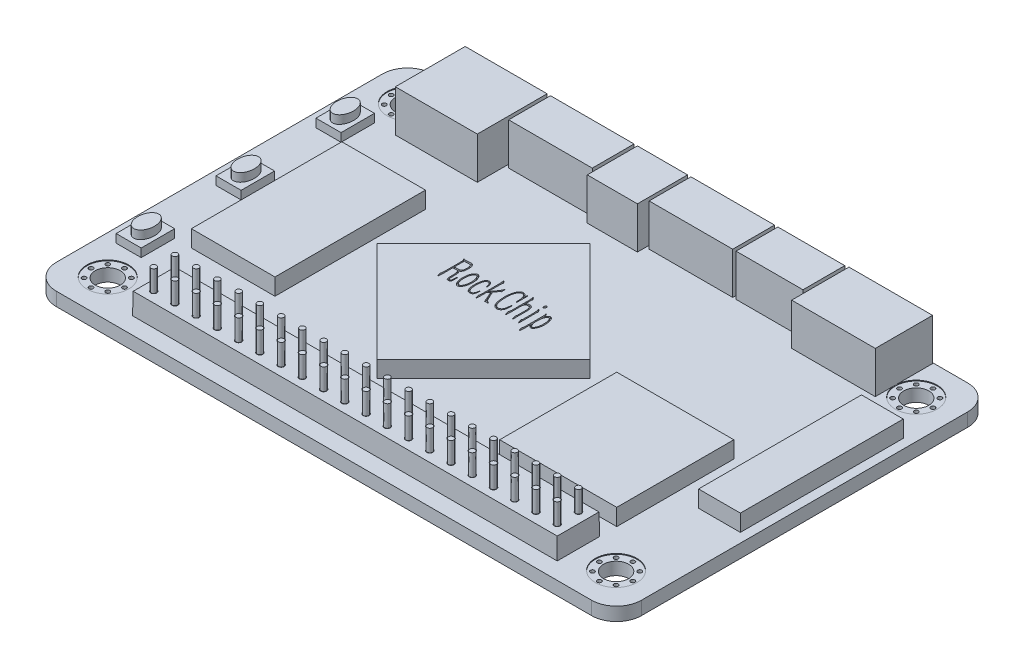
SolidWorks part; units mm, degrees
ref_plane "前视基准面" through (0, 0, 0) normal (0, 0, 1) x (1, 0, 0)
ref_plane "上视基准面" through (0, 0, 0) normal (0, 1, 0) x (1, 0, 0)
ref_plane "右视基准面" through (0, 0, 0) normal (1, 0, 0) x (0, 0, -1)
other "Configuration Table"
sketch "草图1" plane through (0, 0, 0) normal (0, 1, 0) x (1, 0, 0)
  line L0 (0, 33.0521) -> (0, -50.1271) construction
  line L1 (-32, 22.5) -> (32, 22.5)
  line L2 (-35, 19.5) -> (-35, -19.5)
  line L3 (-32, -22.5) -> (32, -22.5)
  line L4 (35, 19.5) -> (35, -19.5)
  line L5 (-35, 22.5) -> (35, -22.5) construction
  line L6 (-35, -22.5) -> (35, 22.5) construction
  line L7 (45.8676, 0) -> (-69.9838, 0) construction
  line L8 (-30.4, 17.95) -> (-30.4, -17.95) construction
  line L9 (-33.4, 13.95) -> (-30.4, 13.95)
  line L10 (-33.4, 13.95) -> (-33.4, 9.95)
  line L11 (-33.4, 9.95) -> (-30.4, 9.95)
  line L12 (-30.4, 13.95) -> (-30.4, 9.95)
  line L13 (-33.4, 13.95) -> (-30.4, 9.95) construction
  line L14 (-33.4, 9.95) -> (-30.4, 13.95) construction
  line L15 (-33.4, 2) -> (-30.4, 2)
  line L16 (-33.4, 2) -> (-33.4, -2)
  line L17 (-33.4, -2) -> (-30.4, -2)
  line L18 (-30.4, 2) -> (-30.4, -2)
  line L19 (-33.4, 2) -> (-30.4, -2) construction
  line L20 (-33.4, -2) -> (-30.4, 2) construction
  line L21 (-33.4, -9.95) -> (-30.4, -9.95)
  line L22 (-33.4, -9.95) -> (-33.4, -13.95)
  line L23 (-33.4, -13.95) -> (-30.4, -13.95)
  line L24 (-30.4, -9.95) -> (-30.4, -13.95)
  line L25 (-33.4, -9.95) -> (-30.4, -13.95) construction
  line L26 (-33.4, -13.95) -> (-30.4, -9.95) construction
  line L27 (-36.5276, -17.95) -> (-25.6215, -17.95) construction
  line L28 (-30.4, -23.6201) -> (-30.4, -14.4561) construction
  line L29 (-27.6395, -15.1895) -> (-32.9892, -20.5392) construction
  line L30 (-32.837, -15.513) -> (-27.2268, -21.1232) construction
  line L31 (-30.4, -24.4793) -> (-30.4, -15.3152) construction
  line L32 (-32.2706, -22.5293) -> (-32.2706, -13.3652) construction
  circle A0 centre (-30.4, -17.95) radius 1.5
  circle A1 centre (30.4, -17.95) radius 1.5
  circle A2 centre (-30.4, 17.95) radius 1.5
  circle A3 centre (-30.4, -17.95) radius 2.5
  circle A4 centre (30.4, 17.95) radius 1.5
  circle A5 centre (30.4, 17.95) radius 2.5
  circle A6 centre (30.4, -17.95) radius 2.5
  circle A7 centre (-30.4, 17.95) radius 2.5
  arc A8 (32, -22.5) -> (35, -19.5) centre (32, -19.5) ccw
  arc A9 (32, 22.5) -> (35, 19.5) centre (32, 19.5) cw
  arc A10 (-32, 22.5) -> (-35, 19.5) centre (-32, 19.5) ccw
  arc A11 (-35, -19.5) -> (-32, -22.5) centre (-32, -19.5) ccw
  circle A12 centre (-28.9858, -16.5358) radius 0.25
  circle A13 centre (-28.4, -17.95) radius 0.25
  circle A14 centre (-30.4, -19.95) radius 0.25
  circle A15 centre (-31.8142, -19.3642) radius 0.25
  circle A16 centre (-31.8142, -16.5358) radius 0.25
  circle A17 centre (-30.4, -15.95) radius 0.25
  circle A18 centre (-32.4, -17.95) radius 0.25
  circle A19 centre (-28.9858, -19.3642) radius 0.25
  circle A20 centre (32.4, -17.95) radius 0.25
  circle A21 centre (31.8142, -19.3642) radius 0.25
  circle A22 centre (30.4, -19.95) radius 0.25
  circle A23 centre (28.9858, -19.3642) radius 0.25
  circle A24 centre (28.4, -17.95) radius 0.25
  circle A25 centre (28.9858, -16.5358) radius 0.25
  circle A26 centre (30.4, -15.95) radius 0.25
  circle A27 centre (31.8142, -16.5358) radius 0.25
  circle A28 centre (31.8142, 16.5358) radius 0.25
  circle A29 centre (30.4, 15.95) radius 0.25
  circle A30 centre (28.9858, 16.5358) radius 0.25
  circle A31 centre (28.4, 17.95) radius 0.25
  circle A32 centre (28.9858, 19.3642) radius 0.25
  circle A33 centre (30.4, 19.95) radius 0.25
  circle A34 centre (31.8142, 19.3642) radius 0.25
  circle A35 centre (32.4, 17.95) radius 0.25
  circle A36 centre (-32.4, 17.95) radius 0.25
  circle A37 centre (-31.8142, 19.3642) radius 0.25
  circle A38 centre (-30.4, 19.95) radius 0.25
  circle A39 centre (-28.9858, 19.3642) radius 0.25
  circle A40 centre (-28.4, 17.95) radius 0.25
  circle A41 centre (-28.9858, 16.5358) radius 0.25
  circle A42 centre (-30.4, 15.95) radius 0.25
  circle A43 centre (-31.8142, 16.5358) radius 0.25
  ellipse E0 centre (-31.9, 11.95) end of major axis (-31.9, 13.45) minor radius 1
  ellipse E1 centre (-31.8382, 0.0298) end of major axis (-31.8382, 1.5298) minor radius 1
  ellipse E2 centre (-31.8627, -11.883) end of major axis (-31.8627, -10.383) minor radius 1
  point P0 (0, 0)
  point P38 (-31.9, 11.95)
  point P43 (-31.9, 0)
  point P48 (-31.9, -11.95)
  dimension "D4" = 35.9
  dimension "D5" = 3
  dimension "D8" = 3
  dimension "D20" = 90
  dimension "D22" = 2
  dimension "D23" = 0.5
  dimension "D25" = 2
  dimension "D29" = 2
  dimension "D1" = 45
  dimension "D2" = 70
  dimension "D3" = 60.8
  dimension "D9" = 6
  dimension "D10" = 6
  dimension "D11" = 3
  dimension "D12" = 3
  dimension "D13" = 3
  dimension "D14" = 4
  dimension "D15" = 4
  dimension "D16" = 4
  dimension "D17" = 17.95
  dimension "D18" = 2
  dimension "D19" = 3
  dimension "D21" = 45
  dimension "D24" = 2
  dimension "D26" = 2
  dimension "D27" = 2
  dimension "D28" = 2
  dimension "D30" = 2
  dimension "D6" = 1
  dimension "D7" = 1
extrude "凸台-拉伸1" add sketch "草图1" along normal blind 1.6 contours L1 A9 L4 A8 L3 A11 L2 A10
extrude "切除-拉伸2" cut sketch "草图1<4>" against normal through all and the other way through all contours A4 | A0 | A2 | A1 region at (30.4, 0, -17.95)
sketch "草图1<4>" plane through (0, 0, 0) normal (0, 1, 0) x (1, 0, 0) same geometry as "草图1"
extrude "凸台-拉伸4" add sketch "草图1<6>" along normal blind 1 from surface contours L9 L12 L11 L10 | L15 L18 L17 L16 | L21 L24 L23 L22 starting at face at (-30.4, 1.6, -19.45)
sketch "草图1<6>" plane through (0, 0, 0) normal (0, 1, 0) x (1, 0, 0) same geometry as "草图1"
extrude "凸台-拉伸5" add sketch "草图1<7>" along normal blind 1 from surface contours E1 | E0 | E2 starting at face at (-31.9, 2.6, 0)
sketch "草图1<7>" plane through (0, 0, 0) normal (0, 1, 0) x (1, 0, 0) same geometry as "草图1"
extrude "切除-拉伸3" cut sketch "草图1<8>" against normal blind 0.1 from surface contours A3 | A6 | A5 | A7 starting at face at (-31.9, 1.6, -11.95)
sketch "草图1<8>" plane through (0, 0, 0) normal (0, 1, 0) x (1, 0, 0) same geometry as "草图1"
extrude "切除-拉伸4" cut sketch "草图1<9>" against normal through all from surface contours A13 | A19 | A14 | A36 | A34 | A35 | A28 | A29 | A30 | A31 | A32 | A12 | A15 | A18 | A16 | A17 | A39 | A40 | A41 | A42 | A43 | A37 | A38 | A33 | A27 | A26 | A25 | A24 | A23 | A22 | A21 | A20 region at (-28.4, 0, 17.95) region at (-30.4, 0, 19.95) region at (-28.9858, 0, 19.3642) region at (31.8142, 0, -16.5358) region at (30.4, 0, -15.95) region at (28.9858, 0, -16.5358) region at (28.4, 0, -17.95) region at (28.9858, 0, -19.3642) region at (31.8142, 0, -19.3642) region at (32.4, 0, -17.95) region at (-32.4, 0, -17.95) starting at face at (-30.4, 1.6, -15.45)
sketch "草图1<9>" plane through (0, 0, 0) normal (0, 1, 0) x (1, 0, 0) same geometry as "草图1"
sketch "草图2" plane through (0, 1.6, 0) normal (0, 1, 0) x (1, 0, 0)
  line L0 (-32, 22.5) -> (32, 22.5) construction
  line L1 (17.9, 22.4) -> (27.9, 22.4)
  line L2 (17.9, 22.4) -> (17.9, 15.55)
  line L3 (17.9, 15.55) -> (27.9, 15.55)
  line L4 (27.9, 22.4) -> (27.9, 15.55)
  line L5 (17.9, 22.4) -> (27.9, 15.55) construction
  line L6 (17.9, 15.55) -> (27.9, 22.4) construction
  line L7 (9.5, 22.3) -> (17.5, 22.3)
  line L8 (9.5, 22.3) -> (9.5, 17.3)
  line L9 (9.5, 17.3) -> (17.5, 17.3)
  line L10 (17.5, 22.3) -> (17.5, 17.3)
  line L11 (9.5, 22.3) -> (17.5, 17.3) construction
  line L12 (9.5, 17.3) -> (17.5, 22.3) construction
  line L13 (-0.9, 22.3) -> (9.1, 22.3)
  line L14 (-0.9, 22.3) -> (-0.9, 17.3)
  line L15 (-0.9, 17.3) -> (9.1, 17.3)
  line L16 (9.1, 22.3) -> (9.1, 17.3)
  line L17 (-0.9, 22.3) -> (9.1, 17.3) construction
  line L18 (-0.9, 17.3) -> (9.1, 22.3) construction
  line L19 (-7.3, 22.3) -> (-1.3, 22.3)
  line L20 (-7.3, 22.3) -> (-7.3, 16.3)
  line L21 (-7.3, 16.3) -> (-1.3, 16.3)
  line L22 (-1.3, 22.3) -> (-1.3, 16.3)
  line L23 (-7.3, 22.3) -> (-1.3, 16.3) construction
  line L24 (-7.3, 16.3) -> (-1.3, 22.3) construction
  line L25 (-30.4, 13.95) -> (-33.4, 13.95) construction
  line L26 (-17.7, 22.3) -> (-7.7, 22.3)
  line L27 (-17.7, 22.3) -> (-17.7, 17.3)
  line L28 (-17.7, 17.3) -> (-7.7, 17.3)
  line L29 (-7.7, 22.3) -> (-7.7, 17.3)
  line L30 (-17.7, 22.3) -> (-7.7, 17.3) construction
  line L31 (-17.7, 17.3) -> (-7.7, 22.3) construction
  line L32 (-27.9, 22.3) -> (-18.1, 22.3)
  line L33 (-27.9, 22.3) -> (-27.9, 13.95)
  line L34 (-27.9, 13.95) -> (-18.1, 13.95)
  line L35 (-18.1, 22.3) -> (-18.1, 13.95)
  line L36 (-27.9, 22.3) -> (-18.1, 13.95) construction
  line L37 (-27.9, 13.95) -> (-18.1, 22.3) construction
  circle A0 centre (30.4, 17.95) radius 2.5 construction
  circle A1 centre (-30.4, 17.95) radius 2.5 construction
  circle A3 centre (30.4, 17.95) radius 2.5 construction
  point P0 (22.9, 18.975)
  point P5 (13.5, 19.8)
  point P10 (4.1, 19.8)
  point P15 (2.2823, 22.5)
  point P22 (-12.7, 19.8)
  point P27 (-23, 18.125)
  point P37 (-17.7, 19.8)
  dimension "D1" = 0.1
  dimension "D2" = 0.4
  dimension "D3" = 10
  dimension "D4" = 0.1
  dimension "D5" = 0.2
  dimension "D6" = 8
  dimension "D7" = 5
  dimension "D8" = 0.4
  dimension "D9" = 0.2
  dimension "D10" = 10
  dimension "D11" = 5
  dimension "D12" = 0.4
  dimension "D13" = 0.2
  dimension "D14" = 6
  dimension "D15" = 6
  dimension "D16" = 0.4
  dimension "D17" = 0.2
  dimension "D18" = 10
  dimension "D19" = 5
  dimension "D20" = 0.4
  dimension "D21" = 0.2
  dimension "D22" = 0
  dimension "D23" = 0
extrude "凸台-拉伸6" add sketch "草图2" along normal blind 5
sketch "草图4" plane through (0, 1.6, 0) normal (0, 1, 0) x (1, 0, 0)
  line L0 (-15.7744, -0.3536) -> (-3.0464, 12.3744)
  line L1 (-28.4, 8.05) -> (-18.4, 8.05)
  line L2 (-28.4, 8.05) -> (-28.4, -9.95)
  line L3 (-28.4, -9.95) -> (-18.4, -9.95)
  line L4 (-18.4, 8.05) -> (-18.4, -9.95)
  line L5 (-28.4, 8.05) -> (-18.4, -9.95) construction
  line L6 (-28.4, -9.95) -> (-18.4, 8.05) construction
  line L7 (-15.7744, -0.3536) -> (-3.7536, -12.3744)
  line L8 (-3.0464, 12.3744) -> (8.9744, 0.3536)
  line L9 (-3.7536, -12.3744) -> (8.9744, 0.3536)
  line L10 (-15.7744, -0.3536) -> (8.9744, 0.3536) construction
  line L11 (-3.0464, 12.3744) -> (-3.7536, -12.3744) construction
  line L12 (0, 0) -> (51.299, 0) construction
  line L13 (-30.4, -2) -> (-30.4, 2) construction
  line L14 (-32, 22.5) -> (32, 22.5) construction
  line L15 (-30.4, -9.95) -> (-33.4, -9.95) construction
  line L16 (-32, -22.5) -> (32, -22.5) construction
  line L17 (-30.4, -17.95) -> (30.4, -17.95) construction
  line L18 (-24.9, -15.41) -> (-22.36, -15.41)
  line L19 (-24.9, -15.41) -> (-24.9, -20.49)
  line L20 (-24.9, -20.49) -> (-22.36, -20.49)
  line L21 (-22.36, -15.41) -> (-22.36, -20.49)
  line L22 (-24.9, -15.41) -> (-22.36, -20.49) construction
  line L23 (-24.9, -20.49) -> (-22.36, -15.41) construction
  line L24 (-24.9, -17.95) -> (-22.36, -17.95)
  line L25 (-22.36, -15.41) -> (-22.36, -20.49)
  line L26 (-22.36, -15.41) -> (-19.82, -15.41)
  line L27 (-19.82, -15.41) -> (-19.82, -20.49)
  line L28 (-22.36, -20.49) -> (-19.82, -20.49)
  line L29 (-22.36, -17.95) -> (-19.82, -17.95)
  line L30 (-19.82, -15.41) -> (-19.82, -20.49)
  line L31 (-19.82, -15.41) -> (-17.28, -15.41)
  line L32 (-17.28, -15.41) -> (-17.28, -20.49)
  line L33 (-19.82, -20.49) -> (-17.28, -20.49)
  line L34 (-19.82, -17.95) -> (-17.28, -17.95)
  line L35 (-17.28, -15.41) -> (-17.28, -20.49)
  line L36 (-17.28, -15.41) -> (-14.74, -15.41)
  line L37 (-14.74, -15.41) -> (-14.74, -20.49)
  line L38 (-17.28, -20.49) -> (-14.74, -20.49)
  line L39 (-17.28, -17.95) -> (-14.74, -17.95)
  line L40 (-14.74, -15.41) -> (-14.74, -20.49)
  line L41 (-14.74, -15.41) -> (-12.2, -15.41)
  line L42 (-12.2, -15.41) -> (-12.2, -20.49)
  line L43 (-14.74, -20.49) -> (-12.2, -20.49)
  line L44 (-14.74, -17.95) -> (-12.2, -17.95)
  line L45 (-12.2, -15.41) -> (-12.2, -20.49)
  line L46 (-12.2, -15.41) -> (-9.66, -15.41)
  line L47 (-9.66, -15.41) -> (-9.66, -20.49)
  line L48 (-12.2, -20.49) -> (-9.66, -20.49)
  line L49 (-12.2, -17.95) -> (-9.66, -17.95)
  line L50 (-9.66, -15.41) -> (-9.66, -20.49)
  line L51 (-9.66, -15.41) -> (-7.12, -15.41)
  line L52 (-7.12, -15.41) -> (-7.12, -20.49)
  line L53 (-9.66, -20.49) -> (-7.12, -20.49)
  line L54 (-9.66, -17.95) -> (-7.12, -17.95)
  line L55 (-7.12, -15.41) -> (-7.12, -20.49)
  line L56 (-7.12, -15.41) -> (-4.58, -15.41)
  line L57 (-4.58, -15.41) -> (-4.58, -20.49)
  line L58 (-7.12, -20.49) -> (-4.58, -20.49)
  line L59 (-7.12, -17.95) -> (-4.58, -17.95)
  line L60 (-4.58, -15.41) -> (-4.58, -20.49)
  line L61 (-4.58, -15.41) -> (-2.04, -15.41)
  line L62 (-2.04, -15.41) -> (-2.04, -20.49)
  line L63 (-4.58, -20.49) -> (-2.04, -20.49)
  line L64 (-4.58, -17.95) -> (-2.04, -17.95)
  line L65 (-2.04, -15.41) -> (-2.04, -20.49)
  line L66 (-2.04, -15.41) -> (0.5, -15.41)
  line L67 (0.5, -15.41) -> (0.5, -20.49)
  line L68 (-2.04, -20.49) -> (0.5, -20.49)
  line L69 (-2.04, -17.95) -> (0.5, -17.95)
  line L70 (0.5, -15.41) -> (0.5, -20.49)
  line L71 (0.5, -15.41) -> (3.04, -15.41)
  line L72 (3.04, -15.41) -> (3.04, -20.49)
  line L73 (0.5, -20.49) -> (3.04, -20.49)
  line L74 (0.5, -17.95) -> (3.04, -17.95)
  line L75 (3.04, -15.41) -> (3.04, -20.49)
  line L76 (3.04, -15.41) -> (5.58, -15.41)
  line L77 (5.58, -15.41) -> (5.58, -20.49)
  line L78 (3.04, -20.49) -> (5.58, -20.49)
  line L79 (3.04, -17.95) -> (5.58, -17.95)
  line L80 (5.58, -15.41) -> (5.58, -20.49)
  line L81 (5.58, -15.41) -> (8.12, -15.41)
  line L82 (8.12, -15.41) -> (8.12, -20.49)
  line L83 (5.58, -20.49) -> (8.12, -20.49)
  line L84 (5.58, -17.95) -> (8.12, -17.95)
  line L85 (8.12, -15.41) -> (8.12, -20.49)
  line L86 (8.12, -15.41) -> (10.66, -15.41)
  line L87 (10.66, -15.41) -> (10.66, -20.49)
  line L88 (8.12, -20.49) -> (10.66, -20.49)
  line L89 (8.12, -17.95) -> (10.66, -17.95)
  line L90 (10.66, -15.41) -> (10.66, -20.49)
  line L91 (10.66, -15.41) -> (13.2, -15.41)
  line L92 (13.2, -15.41) -> (13.2, -20.49)
  line L93 (10.66, -20.49) -> (13.2, -20.49)
  line L94 (10.66, -17.95) -> (13.2, -17.95)
  line L95 (13.2, -15.41) -> (13.2, -20.49)
  line L96 (13.2, -15.41) -> (15.74, -15.41)
  line L97 (15.74, -15.41) -> (15.74, -20.49)
  line L98 (13.2, -20.49) -> (15.74, -20.49)
  line L99 (13.2, -17.95) -> (15.74, -17.95)
  line L100 (15.74, -15.41) -> (15.74, -20.49)
  line L101 (15.74, -15.41) -> (18.28, -15.41)
  line L102 (18.28, -15.41) -> (18.28, -20.49)
  line L103 (15.74, -20.49) -> (18.28, -20.49)
  line L104 (15.74, -17.95) -> (18.28, -17.95)
  line L105 (18.28, -15.41) -> (18.28, -20.49)
  line L106 (18.28, -15.41) -> (20.82, -15.41)
  line L107 (20.82, -15.41) -> (20.82, -20.49)
  line L108 (18.28, -20.49) -> (20.82, -20.49)
  line L109 (18.28, -17.95) -> (20.82, -17.95)
  line L110 (20.82, -15.41) -> (20.82, -20.49)
  line L111 (20.82, -15.41) -> (23.36, -15.41)
  line L112 (23.36, -15.41) -> (23.36, -20.49)
  line L113 (20.82, -20.49) -> (23.36, -20.49)
  line L114 (20.82, -17.95) -> (23.36, -17.95)
  line L115 (23.36, -15.41) -> (23.36, -20.49)
  line L116 (23.36, -15.41) -> (25.9, -15.41)
  line L117 (25.9, -15.41) -> (25.9, -20.49)
  line L118 (23.36, -20.49) -> (25.9, -20.49)
  line L119 (23.36, -17.95) -> (25.9, -17.95)
  line L121 (11.9, 0.6278) -> (25.9, 0.6278)
  line L122 (11.9, 0.6278) -> (11.9, -13.3722)
  line L123 (11.9, -13.3722) -> (25.9, -13.3722)
  line L124 (25.9, 0.6278) -> (25.9, -13.3722)
  line L125 (11.9, 0.6278) -> (25.9, -13.3722) construction
  line L126 (11.9, -13.3722) -> (25.9, 0.6278) construction
  line L127 (28.8899, 12.9069) -> (33.8898, 12.9069)
  line L128 (28.8899, 12.9069) -> (28.8899, -6.578)
  line L129 (28.8899, -6.578) -> (33.8898, -6.578)
  line L130 (33.8898, 12.9069) -> (33.8898, -6.578)
  circle A5 centre (-23.63, -19.22) radius 0.32
  circle A6 centre (-23.63, -16.68) radius 0.32
  circle A7 centre (-21.09, -16.68) radius 0.32
  circle A8 centre (-21.09, -19.22) radius 0.32
  circle A9 centre (-18.55, -16.68) radius 0.32
  circle A10 centre (-18.55, -19.22) radius 0.32
  circle A11 centre (-16.01, -16.68) radius 0.32
  circle A12 centre (-16.01, -19.22) radius 0.32
  circle A13 centre (-13.47, -16.68) radius 0.32
  circle A14 centre (-13.47, -19.22) radius 0.32
  circle A15 centre (-10.93, -16.68) radius 0.32
  circle A16 centre (-10.93, -19.22) radius 0.32
  circle A17 centre (-8.39, -16.68) radius 0.32
  circle A18 centre (-8.39, -19.22) radius 0.32
  circle A19 centre (-5.85, -16.68) radius 0.32
  circle A20 centre (-5.85, -19.22) radius 0.32
  circle A21 centre (-3.31, -16.68) radius 0.32
  circle A22 centre (-3.31, -19.22) radius 0.32
  circle A23 centre (-0.77, -16.68) radius 0.32
  circle A24 centre (-0.77, -19.22) radius 0.32
  circle A25 centre (1.77, -16.68) radius 0.32
  circle A26 centre (1.77, -19.22) radius 0.32
  circle A27 centre (4.31, -16.68) radius 0.32
  circle A28 centre (4.31, -19.22) radius 0.32
  circle A29 centre (6.85, -16.68) radius 0.32
  circle A30 centre (6.85, -19.22) radius 0.32
  circle A31 centre (9.39, -16.68) radius 0.32
  circle A32 centre (9.39, -19.22) radius 0.32
  circle A33 centre (11.93, -16.68) radius 0.32
  circle A34 centre (11.93, -19.22) radius 0.32
  circle A35 centre (14.47, -16.68) radius 0.32
  circle A36 centre (14.47, -19.22) radius 0.32
  circle A37 centre (17.01, -16.68) radius 0.32
  circle A38 centre (17.01, -19.22) radius 0.32
  circle A39 centre (19.55, -16.68) radius 0.32
  circle A40 centre (19.55, -19.22) radius 0.32
  circle A41 centre (22.09, -16.68) radius 0.32
  circle A42 centre (22.09, -19.22) radius 0.32
  circle A43 centre (24.63, -16.68) radius 0.32
  circle A44 centre (24.63, -19.22) radius 0.32
  circle A46 centre (-30.4, -17.95) radius 2.5 construction
  point P0 (-23.4, -1.509)
  point P6 (-3.4, 0)
  point P36 (18.9, -6.3722)
  dimension "D10" = 1.27
  dimension "D12" = 0.64
  dimension "D13" = 20
  dimension "D1" = 45
  dimension "D2" = 10
  dimension "D3" = 2
  dimension "D4" = 18
  dimension "D5" = 18
  dimension "D6" = 17
  dimension "D7" = 15
  dimension "D8" = 2.54
  dimension "D9" = 5.08
  dimension "D11" = 1.27
  dimension "D14" = 3
  dimension "D15" = 14
extrude "凸台-拉伸7" add sketch "草图4" along normal blind 2 contours L4 L1 L2 L3 | L7 L9 L8 L0 | L124 L121 L122 L123 | L130 L127 L128 L129 region at (-3.4, 1.6, 0) region at (-23.4, 1.6, 0.95) region at (18.9, 1.6, 6.3722) region at (31.3899, 1.6, -3.1645)
sketch "草图5" plane through (0, 3.6, 0) normal (0, 1, 0) x (1, 0, 0)
  text T0 "RockChip"
extrude "切除-拉伸7" cut sketch "草图5" against normal blind 0.2
extrude "凸台-拉伸9" add sketch "草图4<5>" along normal blind 2.54 draft 1 contours L19 L24 L21 L18 A6 | L21 L29 L27 L26 A7 | L29 L21 L28 L27 A8 | L24 L19 L20 L21 A5 | L34 L27 L33 L32 A10 | L27 L34 L32 L31 A9 | L32 L39 L37 L36 A11 | L44 L37 L43 L42 A14 | L39 L32 L38 L37 A12 | L37 L44 L42 L41 A13 | L42 L49 L47 L46 A15 | L47 L54 L52 L51 A17 | L54 L47 L53 L52 A18 | L49 L42 L48 L47 A16 | L59 L52 L58 L57 A20 | L52 L59 L57 L56 A19 | L57 L64 L62 L61 A21 | L62 L69 L67 L66 A23 | L69 L62 L68 L67 A24 | L64 L57 L63 L62 A22 | L67 L74 L72 L71 A25 | L74 L67 L73 L72 A26 | L72 L79 L77 L76 A27 | L79 L72 L78 L77 A28 | L84 L77 L83 L82 A30 | L77 L84 L82 L81 A29 | L82 L89 L87 L86 A31 | L89 L82 L88 L87 A32 | L87 L94 L92 L91 A33 | L94 L87 L93 L92 A34 | L99 L92 L98 L97 A36 | L92 L99 L97 L96 A35 | L97 L104 L102 L101 A37 | L104 L97 L103 L102 A38 | L119 L112 L118 L117 A44 | L114 L107 L113 L112 A42 | L112 L119 L117 L116 A43 | L107 L114 L112 L111 A41 | L102 L109 L107 L106 A39 | L109 L102 L108 L107 A40 region at (-23.63, 1.6, 15.4459) region at (-21.09, 1.6, 15.4459) region at (-23.63, 1.6, 17.9859) region at (-21.09, 1.6, 17.9859) region at (-18.55, 1.6, 15.4459) region at (-18.55, 1.6, 17.9859) region at (-16.01, 1.6, 15.4459) region at (-16.01, 1.6, 17.9859) region at (-13.47, 1.6, 15.4459) region at (-13.47, 1.6, 17.9859) region at (-10.93, 1.6, 15.4459) region at (-10.93, 1.6, 17.9859) region at (-8.39, 1.6, 15.4459) region at (-8.39, 1.6, 17.9859) region at (-5.85, 1.6, 15.4459) region at (-5.85, 1.6, 17.9859) region at (-3.31, 1.6, 15.4459) region at (-3.31, 1.6, 17.9859) region at (-0.77, 1.6, 15.4459) region at (-0.77, 1.6, 17.9859) region at (1.77, 1.6, 15.4459) region at (1.77, 1.6, 17.9859) region at (4.31, 1.6, 15.4459) region at (4.31, 1.6, 17.9859) region at (6.85, 1.6, 15.4459) region at (6.85, 1.6, 17.9859) region at (9.39, 1.6, 15.4459) region at (9.39, 1.6, 17.9859) region at (11.93, 1.6, 15.4459) region at (11.93, 1.6, 17.9859) region at (14.47, 1.6, 15.4459) region at (14.47, 1.6, 17.9859) region at (17.01, 1.6, 15.4459) region at (17.01, 1.6, 17.9859) region at (19.55, 1.6, 15.4459) region at (19.55, 1.6, 17.9859) region at (22.09, 1.6, 15.4459) region at (22.09, 1.6, 17.9859) region at (24.63, 1.6, 15.4459) region at (24.63, 1.6, 17.9859)
sketch "草图4<5>" plane through (0, 1.6, 0) normal (0, 1, 0) x (1, 0, 0) same geometry as "草图4"
extrude "凸台-拉伸10" add sketch "草图4<6>" along normal blind 2.54 from surface separate body contours A16 | A18 | A6 | A5 | A7 | A8 | A10 | A9 | A11 | A12 | A13 | A14 | A15 | A17 | A19 | A20 | A21 | A22 | A23 | A24 | A25 | A26 | A27 | A28 | A29 | A30 | A31 | A32 | A33 | A34 | A35 | A36 | A37 | A38 | A39 | A40 | A41 | A42 | A43 | A44 region at (-10.93, 1.6, 19.22) region at (-8.39, 1.6, 19.22) starting at face at (0.5, 4.14, 17.95)
sketch "草图4<6>" plane through (0, 1.6, 0) normal (0, 1, 0) x (1, 0, 0) same geometry as "草图4"
